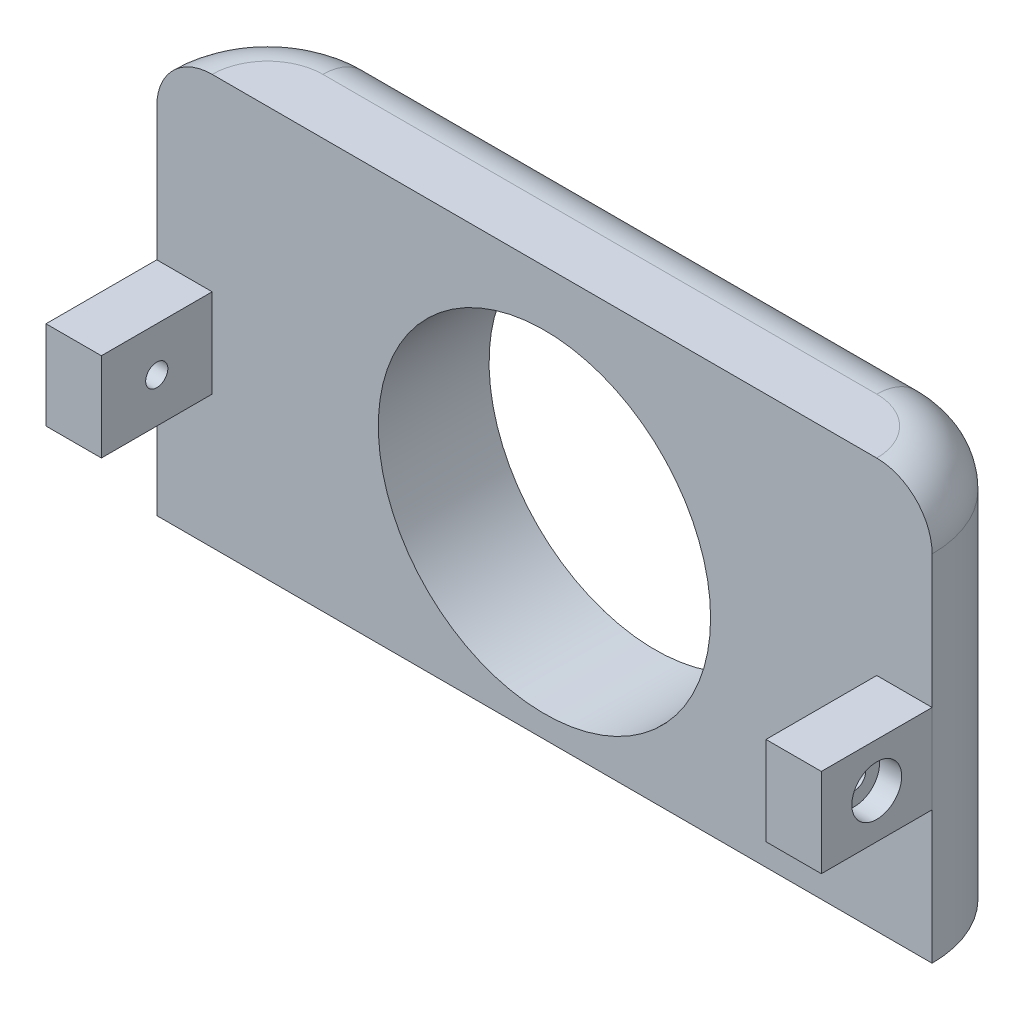
SolidWorks part; units mm, degrees
material "LW PLA"
ref_plane "Front Plane" through (0, 0, 0) normal (0, 0, 1) x (1, 0, 0)
ref_plane "Top Plane" through (0, 0, 0) normal (0, 1, 0) x (1, 0, 0)
ref_plane "Right Plane" through (0, 0, 0) normal (1, 0, 0) x (0, 0, -1)
sketch "Sketch1" plane through (0, 0, 0) normal (0, 1, 0) x (1, 0, 0)
  line L1 (-25, 0) -> (25, 0)
  line L3 (-35, -10) -> (35, -10)
  arc A0 (-35, -10) -> (-25, 0) centre (-25, -10) cw
  arc A1 (35, -10) -> (25, 0) centre (25, -10) ccw
extrude "Boss-Extrude1" add sketch "Sketch1" along normal blind 37
sketch "Sketch3" plane through (0, 0, 10) normal (0, 0, 1) x (1, 0, 0)
  line L4 (-30, 37) -> (-35, 37)
  line L5 (-35, 37) -> (-35, 0) construction
  line L6 (-35, 37) -> (-35, 32)
  line L7 (30, 37) -> (35, 37)
  line L16 (35, 37) -> (35, 32)
  arc A0 (35, 32) -> (30, 37) centre (30, 32) ccw
  arc A1 (-35, 32) -> (-30, 37) centre (-30, 32) cw
  dimension "D2" = 5
extrude "Cut-Extrude1" cut sketch "Sketch3" against normal up to next
fillet "Fillet1" radius 5 3 edges at (27.5882, 37, 0.3407) (-27.5882, 37, 0.3407) (0, 37, 0)
sketch "Sketch4" plane through (0, 0, 10) normal (0, 0, 1) x (1, 0, 0)
  line L1 (-30, 37) -> (30, 37) construction
  circle A0 centre (0, 17) radius 15
  point P6 (0, 37)
  dimension "D1" = 30
  dimension "D2" = 20
extrude "Cut-Extrude2" cut sketch "Sketch4" against normal up to next
ref_plane "Plane1" through (-35, 0, 0) normal (1, 0, 0) x (0, 0, -1)
sketch "Sketch5" plane through (-35, 0, 0) normal (1, 0, 0) x (0, 0, -1)
  line L0 (-10, 32) -> (-10, 0) construction
  line L1 (-10, 12) -> (-20, 12)
  line L2 (-10, 12) -> (-10, 20)
  line L3 (-10, 20) -> (-20, 20)
  line L4 (-20, 12) -> (-20, 20)
  circle A0 centre (-15, 16) radius 2.25
  circle A1 centre (-15, 16) radius 1
  point P6 (-10, 16)
  point P7 (-10, 16)
  point P14 (-15, 20)
  dimension "D3" = 2
  dimension "D4" = 4.5
  dimension "D1" = 8
  dimension "D2" = 10
extrude "Boss-Extrude2" add sketch "Sketch5" along normal blind 5 contours A0 A1 | L4 L1 L2 L3 A0 region at (-35, 12.1281, 15) region at (-35, 16, 17.1864)
extrude "Cut-Extrude3" cut sketch "Sketch5<3>" along normal blind 2 contours A0 A1 region at (-35, 16, 17.1864)
sketch "Sketch5<3>" plane through (-35, 0, 0) normal (1, 0, 0) x (0, 0, -1) same geometry as "Sketch5"
mirror "Mirror1" about plane through (0, 0, 0) normal (1, 0, 0) of "Cut-Extrude3", "Boss-Extrude2"
